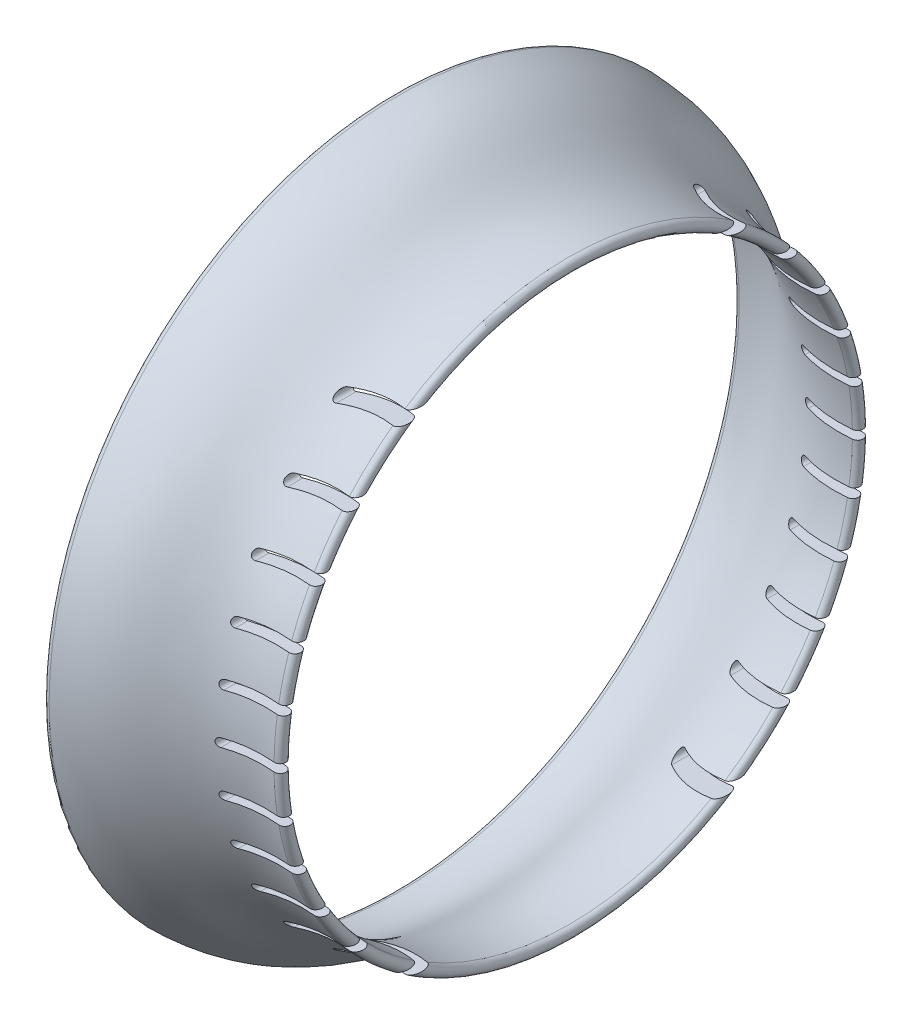
SolidWorks part; units mm, degrees
ref_plane "Front Plane" through (0, 0, 0) normal (0, 0, 1) x (1, 0, 0)
ref_plane "Top Plane" through (0, 0, 0) normal (0, 1, 0) x (1, 0, 0)
ref_plane "Right Plane" through (0, 0, 0) normal (1, 0, 0) x (0, 0, -1)
sketch "Sketch1" plane through (0, 0, 0) normal (0, 0, 1) x (1, 0, 0)
  line L0 (52.8242, 74.1272) -> (39.0703, 72.8836) construction
  line L1 (39.0703, 72.8836) -> (35.3113, 81.923) construction
  line L2 (35.3113, 81.923) -> (30.0309, 83.8025) construction
  line L3 (30.0309, 83.8025) -> (22.8242, 84.1272) construction
  line L6 (-45.9253, 24.1272) -> (83.8871, 24.1272) construction
  arc A0 (22.9143, 86.1252) -> (22.8242, 84.1272) centre (22.8692, 85.1262) ccw
  arc A1 (52.6441, 76.1191) -> (52.8242, 74.1272) centre (52.7342, 75.1232) cw
  spline S0 degree 4 poles (52.8242, 74.1272) (39.0703, 72.8836) (35.3113, 81.923) (30.0309, 83.8025) (22.8242, 84.1272) knots 0 0 0 0 0 1 1 1 1 1
  spline S1 degree 1 poles (52.6441, 76.1191) (22.9143, 86.1252) knots 0 0 1 1 construction
  spline S2 degree 3 poles (52.6441, 76.1191) (52.384, 76.0956) (51.8555, 76.0563) (50.857, 76.0148) (49.6723, 76.0245) (48.3551, 76.1234) (46.719, 76.3562) (44.8746, 76.8112) (42.2484, 77.7995) (39.4105, 79.3862) (36.3419, 81.475) (33.3177, 83.4203) (30.1036, 84.9419) (27.2049, 85.6964) (24.7889, 86.0136) (23.5363, 86.0972) (22.9143, 86.1252) knots 0 0 0 0 0.015625 0.03125 0.0625 0.09375 0.125 0.1875 0.25 0.375 0.5 0.625 0.75 0.875 0.9375 1 1 1 1
  dimension "D2" = 60
  dimension "D3" = 50
  dimension "D4" = 2
  dimension "D1" = 30
revolve "Revolve1" add sketch "Sketch1" angle 360 about L6
ref_plane "Plane1" through (0, 0, 70) normal (0, 0, 1) x (1, 0, 0)
sketch "Sketch2" plane through (0, 0, 70) normal (0, 0, 1) x (1, 0, 0)
  line L0 (12.503, 24.1191) -> (70.1384, 24.1191)
  line L1 (42.6441, 88.8958) -> (42.6441, -38.1685)
  line L2 (52.6441, 76.1191) -> (52.6441, -27.8646) construction
  line L3 (44.2122, 24.1191) -> (55.6908, 24.1191) construction
  line L4 (44.2122, 24.8691) -> (55.6908, 24.8691)
  line L5 (44.2122, 23.3691) -> (55.6908, 23.3691)
  line L6 (44.2122, 32.6191) -> (55.6908, 32.6191) construction
  line L9 (44.2122, 33.3691) -> (55.6908, 33.3691)
  line L12 (44.2122, 31.8691) -> (55.6908, 31.8691)
  line L15 (44.2122, 41.1191) -> (55.6908, 41.1191) construction
  line L18 (44.2122, 41.8691) -> (55.6908, 41.8691)
  line L21 (44.2122, 40.3691) -> (55.6908, 40.3691)
  line L24 (44.2122, 49.6191) -> (55.6908, 49.6191) construction
  line L27 (44.2122, 50.3691) -> (55.6908, 50.3691)
  line L30 (44.2122, 48.8691) -> (55.6908, 48.8691)
  line L31 (44.2122, 58.1191) -> (55.6908, 58.1191) construction
  line L32 (44.2122, 58.8691) -> (55.6908, 58.8691)
  line L33 (44.2122, 57.3691) -> (55.6908, 57.3691)
  line L34 (44.2122, 66.6191) -> (55.6908, 66.6191) construction
  line L35 (44.2122, 67.3691) -> (55.6908, 67.3691)
  line L36 (44.2122, 65.8691) -> (55.6908, 65.8691)
  line L37 (44.2122, 15.6191) -> (55.6908, 15.6191) construction
  line L38 (44.2122, 14.8691) -> (55.6908, 14.8691)
  line L39 (44.2122, 16.3691) -> (55.6908, 16.3691)
  line L40 (44.2122, 7.1191) -> (55.6908, 7.1191) construction
  line L41 (44.2122, 6.3691) -> (55.6908, 6.3691)
  line L42 (44.2122, 7.8691) -> (55.6908, 7.8691)
  line L43 (44.2122, -1.3809) -> (55.6908, -1.3809) construction
  line L44 (44.2122, -2.1309) -> (55.6908, -2.1309)
  line L45 (44.2122, -0.6309) -> (55.6908, -0.6309)
  line L46 (44.2122, -9.8809) -> (55.6908, -9.8809) construction
  line L47 (44.2122, -10.6309) -> (55.6908, -10.6309)
  line L48 (44.2122, -9.1309) -> (55.6908, -9.1309)
  line L49 (44.2122, -18.3809) -> (55.6908, -18.3809) construction
  line L50 (44.2122, -19.1309) -> (55.6908, -19.1309)
  line L51 (44.2122, -17.6309) -> (55.6908, -17.6309)
  arc A0 (44.2122, 24.8691) -> (44.2122, 23.3691) centre (44.2122, 24.1191) ccw
  arc A1 (55.6908, 23.3691) -> (55.6908, 24.8691) centre (55.6908, 24.1191) ccw
  arc A18 (44.2122, 33.3691) -> (44.2122, 31.8691) centre (44.2122, 32.6191) ccw
  arc A19 (55.6908, 31.8691) -> (55.6908, 33.3691) centre (55.6908, 32.6191) ccw
  arc A20 (44.2122, 41.8691) -> (44.2122, 40.3691) centre (44.2122, 41.1191) ccw
  arc A21 (55.6908, 40.3691) -> (55.6908, 41.8691) centre (55.6908, 41.1191) ccw
  arc A22 (44.2122, 50.3691) -> (44.2122, 48.8691) centre (44.2122, 49.6191) ccw
  arc A23 (55.6908, 48.8691) -> (55.6908, 50.3691) centre (55.6908, 49.6191) ccw
  arc A24 (44.2122, 58.8691) -> (44.2122, 57.3691) centre (44.2122, 58.1191) ccw
  arc A25 (55.6908, 57.3691) -> (55.6908, 58.8691) centre (55.6908, 58.1191) ccw
  arc A26 (44.2122, 67.3691) -> (44.2122, 65.8691) centre (44.2122, 66.6191) ccw
  arc A27 (55.6908, 65.8691) -> (55.6908, 67.3691) centre (55.6908, 66.6191) ccw
  arc A28 (44.2122, 14.8691) -> (44.2122, 16.3691) centre (44.2122, 15.6191) cw
  arc A29 (55.6908, 16.3691) -> (55.6908, 14.8691) centre (55.6908, 15.6191) cw
  arc A30 (44.2122, 6.3691) -> (44.2122, 7.8691) centre (44.2122, 7.1191) cw
  arc A31 (55.6908, 7.8691) -> (55.6908, 6.3691) centre (55.6908, 7.1191) cw
  arc A32 (44.2122, -2.1309) -> (44.2122, -0.6309) centre (44.2122, -1.3809) cw
  arc A33 (55.6908, -0.6309) -> (55.6908, -2.1309) centre (55.6908, -1.3809) cw
  arc A34 (44.2122, -10.6309) -> (44.2122, -9.1309) centre (44.2122, -9.8809) cw
  arc A35 (55.6908, -9.1309) -> (55.6908, -10.6309) centre (55.6908, -9.8809) cw
  arc A36 (44.2122, -19.1309) -> (44.2122, -17.6309) centre (44.2122, -18.3809) cw
  arc A37 (55.6908, -17.6309) -> (55.6908, -19.1309) centre (55.6908, -18.3809) cw
  point P9 (49.9515, 24.1191)
  point P18 (49.9515, 32.6191)
  point P25 (49.9515, 41.1191)
  point P32 (49.9515, 49.6191)
  point P39 (49.9515, 58.1191)
  point P46 (49.9515, 66.6191)
  point P51 (49.9515, 15.6191)
  point P58 (49.9515, 7.1191)
  point P65 (49.9515, -1.3809)
  point P72 (49.9515, -9.8809)
  point P79 (49.9515, -18.3809)
  point P84 (0, 0)
  point P85 (0, 0)
  dimension "D3" = 6
  dimension "D1" = 10
  dimension "D2" = 52
ref_plane "Plane2" through (37.5, 0, 0) normal (1, 0, 0) x (0, 0, -1)
extrude "Cut-Extrude4" cut sketch "Sketch2" against normal through all both contours L36 A27 L35 A26 | L33 A25 L32 A24 | L30 A23 L27 A22 | L21 A21 L18 A20 | L12 A19 L9 A18 | L5 A1 L4 A0 | L38 A29 L39 A28 | L41 A31 L42 A30 | L44 A33 L45 A32 | L47 A35 L48 A34 | L50 A37 L51 A36
